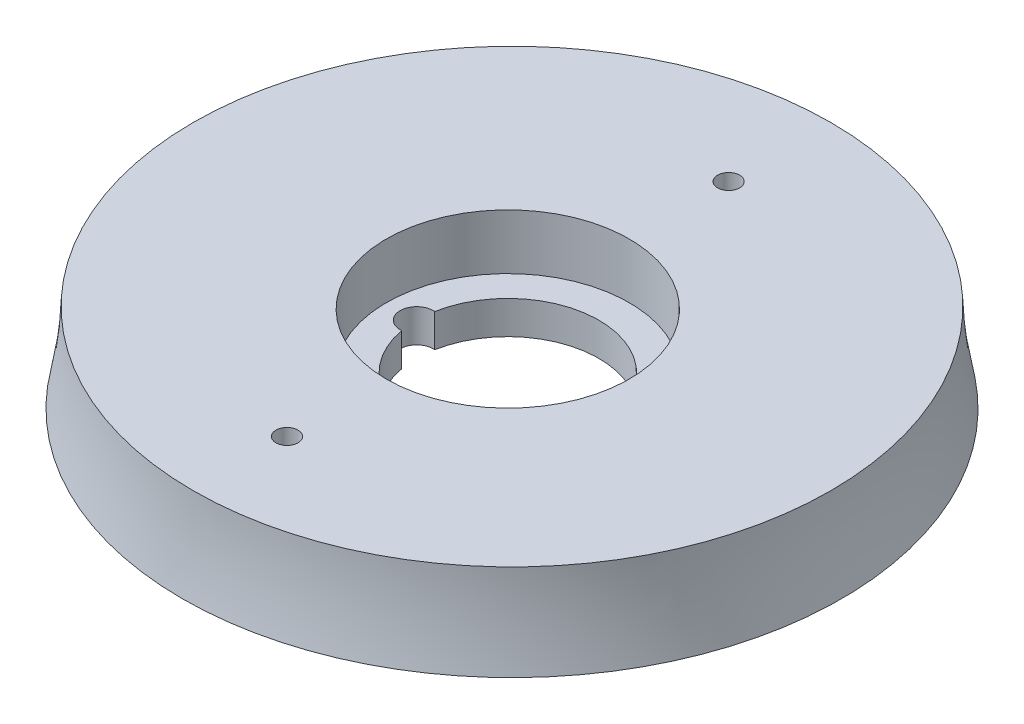
SolidWorks part; units mm, degrees
material "ABS"
ref_plane "Ebene vorne" through (0, 0, 0) normal (0, 0, 1) x (1, 0, 0)
ref_plane "Ebene oben" through (0, 0, 0) normal (0, 1, 0) x (1, 0, 0)
ref_plane "Ebene rechts" through (0, 0, 0) normal (1, 0, 0) x (0, 0, -1)
sketch "Skizze1" plane through (0, 0, 0) normal (1, 0, 0) x (0, 0, -1)
  line L0 (0.3802, 5.0989) -> (0.3802, 63) construction
  line L1 (30.2298, 2.0989) -> (0.3802, 2.0989)
  line L2 (30.2298, 20.0989) -> (30.2298, 2.0989) construction
  line L3 (0.3802, 10.0989) -> (0.3802, 5.0989)
  line L4 (0.3802, 2.0989) -> (0.3802, 5.0989)
  line L5 (0.3802, 10.0989) -> (29.2604, 10.0989)
  line L6 (0.3802, 27.0989) -> (0.3802, 10.0989)
  spline S0 degree 3 poles (0.3802, 27.0989) (8.6312, 27.5228) (14.312, 26.2021) (24.7476, 23.6366) (27.0768, 21.8661) (30.2298, 20.0989) knots 0 0 0 0 0.318831 0.418831 1 1 1 1
  spline S1 degree 3 poles (30.2298, 20.0989) (28.7981, 13.3242) (29.0428, 7.9803) (30.2298, 2.0989) knots 0 0 0 0 1 1 1 1
  dimension "D1" = 30
  dimension "D2" = 7
  dimension "D3" = 22
  dimension "D4" = 8
revolve "Rotation2" add sketch "Skizze1" angle 360 about L0 region at (0, 6.0765, -15.0055)
sketch "Skizze3" plane through (0, 10.0989, 0) normal (0, 1, 0) x (1, 0, 0)
  line L0 (11, 0) -> (-11, 0) construction
  circle A0 centre (0, 0) radius 11
  circle A1 centre (0, 0) radius 8.25
  circle A2 centre (-8.25, 0) radius 1.5
  circle A3 centre (0, 20) radius 1
  circle A4 centre (0, -20) radius 1
  dimension "D1" = 22
  dimension "D2" = 16.5
  dimension "D3" = 2
  dimension "D5" = 3
  dimension "D4" = 20
extrude "Schnitt-Linear austragen3" cut sketch "Skizze3" against normal up to next contours A4 | A3 region at (0, 10.0989, -20) region at (0, 10.0989, 20)
extrude "Schnitt-Linear austragen4" cut sketch "Skizze3<3>" against normal up to next contours A1 L0 A2 | L0 A1 A2 region at (0.1225, 10.0989, 3.548) region at (0.1225, 10.0989, -3.548)
sketch "Skizze3<3>" plane through (0, 10.0989, 0) normal (0, 1, 0) x (1, 0, 0) same geometry as "Skizze3"
extrude "Schnitt-Linear austragen5" cut sketch "Skizze3<4>" against normal blind 5 contours L0 A0 A2 A1 | A0 L0 A1 A2 region at (0, 10.0989, 10.754) region at (9.625, 10.0989, -0.246)
sketch "Skizze3<4>" plane through (0, 10.0989, 0) normal (0, 1, 0) x (1, 0, 0) same geometry as "Skizze3"
extrude "Schnitt-Linear austragen6" cut sketch "Skizze3<5>" against normal up to next contours L0 A2 A1 | L0 A1 A2 | A1 L0 A2 | A2 L0 A1 region at (-7.5895, 10.0989, 0.617) region at (-7.5895, 10.0989, -0.617) region at (-8.8614, 10.0989, -0.6547) region at (-8.8614, 10.0989, 0.6547)
sketch "Skizze3<5>" plane through (0, 10.0989, 0) normal (0, 1, 0) x (1, 0, 0) same geometry as "Skizze3"
